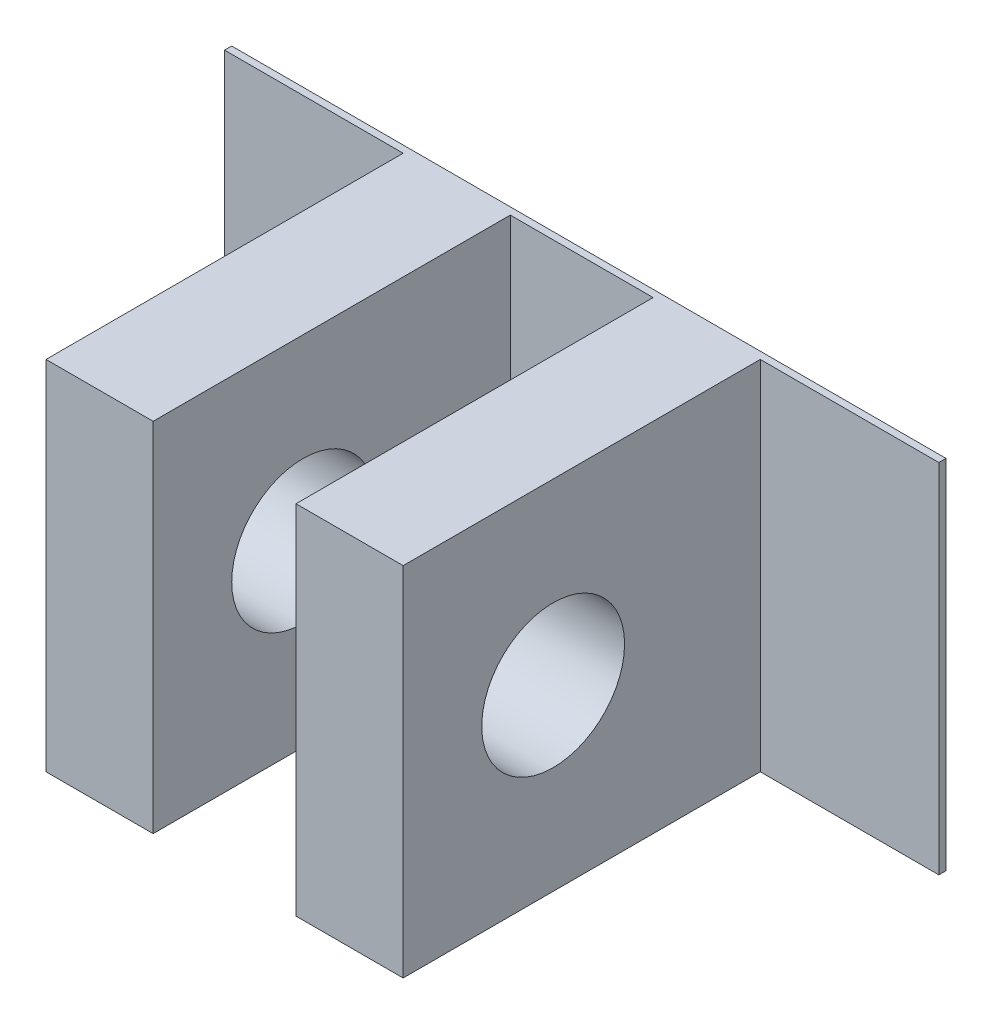
SolidWorks part; units mm, degrees
material "Custom Plastic"
ref_plane "Front Plane" through (0, 0, 0) normal (0, 0, 1) x (1, 0, 0)
ref_plane "Top Plane" through (0, 0, 0) normal (0, 1, 0) x (1, 0, 0)
ref_plane "Right Plane" through (0, 0, 0) normal (1, 0, 0) x (0, 0, -1)
sketch "Servo Rod Holders" plane through (0, 0, 0) normal (0, 0, 1) x (1, 0, 0)
  line L0 (-9.6081, 13.6401) -> (-9.6081, -11.7599)
  line L1 (-9.6081, -11.7599) -> (-1.9881, -11.7599)
  line L2 (-1.9881, -11.7599) -> (-1.9881, 13.6401)
  line L3 (-1.9881, 13.6401) -> (-9.6081, 13.6401)
  line L4 (8.1719, 13.6401) -> (15.7919, 13.6401)
  line L5 (15.7919, 13.6401) -> (15.7919, -11.7599)
  line L6 (15.7919, -11.7599) -> (8.1719, -11.7599)
  line L7 (8.1719, -11.7599) -> (8.1719, 13.6401)
  line L8 (-9.6081, 13.6401) -> (15.7919, 13.6401)
  line L9 (15.7919, -11.7599) -> (-9.6081, -11.7599)
  line L10 (-9.6081, 13.6401) -> (-22.3081, 13.6401)
  line L11 (-22.3081, 13.6401) -> (-22.3081, -11.7599)
  line L12 (-22.3081, -11.7599) -> (-9.6081, -11.7599)
  line L13 (15.7919, 13.6401) -> (28.4919, 13.6401)
  line L14 (28.4919, 13.6401) -> (28.4919, -11.7599)
  line L15 (28.4919, -11.7599) -> (15.7919, -11.7599)
  dimension "D1" = 25.4
  dimension "D2" = 7.62
  dimension "D3" = 10.16
  dimension "D4" = 12.7
  dimension "D5" = 12.7
extrude "Base of the Holders" add sketch "Servo Rod Holders" along normal blind 0.508 contours L9 L7 L8 L2 | L2 L3 L0 L1 | L7 L6 L5 L4 region at (-5.7981, 0.9401, 0) region at (3.0919, 0.9401, 0) region at (11.9819, 0.9401, 0)
extrude "Two Holders Extrude" add sketch "Servo Rod Holders<3>" along normal blind 25.908 contours L7 L6 L5 L4 | L2 L3 L0 L1 region at (-5.7981, 0.9401, 0) region at (11.9819, 0.9401, 0)
sketch "Servo Rod Holders<3>" plane through (0, 0, 0) normal (0, 0, 1) x (1, 0, 0) same geometry as "Servo Rod Holders"
ref_plane "Plane1" through (15.7919, 0, 0) normal (1, 0, 0) x (0, 0, -1)
sketch "Sketch2" plane through (15.7919, 0, 0) normal (1, 0, 0) x (0, 0, -1)
  line L0 (-25.908, 13.6401) -> (0, 13.6401) construction
  line L2 (-25.908, 13.6401) -> (-25.908, -11.7599) construction
  circle A0 centre (-15.24, 0.9401) radius 5.08
  dimension "D1" = 10.16
  dimension "D2" = 12.7
  dimension "D3" = 10.668
extrude "Placement for Rod Extrude Cut" cut sketch "Sketch2" against normal blind 25.4 contours A0 region at (15.7919, 0.9401, 15.24)
extrude "Extension for Screws" add sketch "Servo Rod Holders<4>" along normal blind 0.508 contours L11 L12 L0 L10 | L15 L14 L13 L5 region at (-15.9581, 0.9401, 0) region at (22.1419, 0.9401, 0)
sketch "Servo Rod Holders<4>" plane through (0, 0, 0) normal (0, 0, 1) x (1, 0, 0) same geometry as "Servo Rod Holders"
